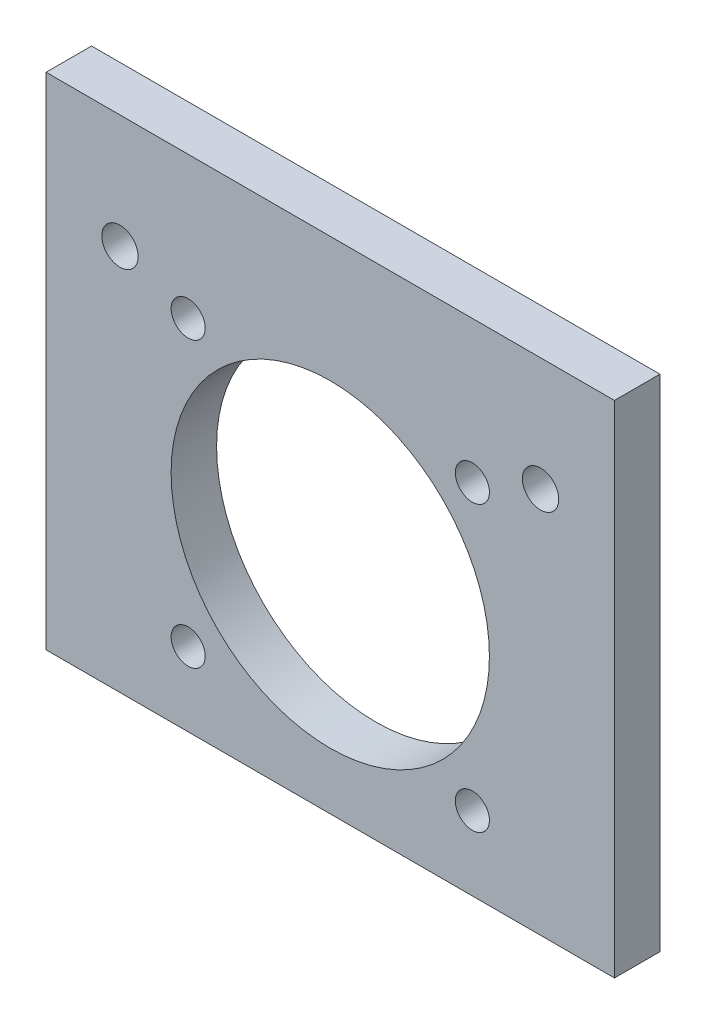
SolidWorks part; units mm, degrees
ref_plane "Płaszczyzna przednia" through (0, 0, 0) normal (0, 0, 1) x (1, 0, 0)
ref_plane "Płaszczyzna górna" through (0, 0, 0) normal (0, 1, 0) x (1, 0, 0)
ref_plane "Płaszczyzna prawa" through (0, 0, 0) normal (1, 0, 0) x (0, 0, -1)
sketch "Sketch1" plane through (0, 0, 0) normal (0, 0, 1) x (1, 0, 0)
  line L1 (0, 0) -> (50, 0)
  line L2 (0, 0) -> (0, 44)
  line L3 (0, 44) -> (50, 44)
  line L4 (50, 0) -> (50, 44)
  dimension "D1" = 50
  dimension "D2" = 44
extrude "Boss-Extrude1" add sketch "Sketch1" along normal blind 4
hole_wizard "Ø3.0mm Dowel Hole1" positions "Sketch2" profile "Sketch3" hole size "Ø3.0" standard "ANSI Metric" end condition through all
sketch "Sketch2" plane through (0, 0, 4) normal (0, 0, 1) x (1, 0, 0)
  line L0 (0, 44) -> (0, 0) construction
  line L1 (50, 44) -> (0, 44) construction
  point P0 (6.5, 34)
  point P2 (43.5, 34)
  dimension "D1" = 37
  dimension "D2" = 6.5
  dimension "D3" = 10
sketch "Sketch3" plane through (6.5, 34, 4) normal (1, 0, 0) x (0, -1, 0)
  line L0 (0, 0) -> (0, 4)
  line L1 (0, 4) -> (1.6, 4)
  line L2 (1.6, 4) -> (1.6, 0)
  line L5 (1.6, 0) -> (0, 0)
  line L11 (0, -6.35) -> (0, 107.95) construction
  dimension "Thru Hole Dia." = 3.2
  dimension "Thru Hole Depth" = 4
sketch "Sketch4" plane through (0, 0, 4) normal (0, 0, 1) x (1, 0, 0)
  line L0 (25, 0) -> (25, 44) construction
  line L1 (0, 0) -> (50, 0) construction
  line L2 (50, 44) -> (0, 44) construction
  circle A0 centre (25, 19) radius 14
  dimension "D1" = 28
  dimension "D2" = 19
extrude "Cut-Extrude1" cut sketch "Sketch4" against normal blind 4
hole_wizard "Ø3.0mm Dowel Hole2" positions "Sketch5" profile "Sketch6" hole size "Ø3.0" standard "ANSI Metric" end condition through all
sketch "Sketch5" plane through (0, 0, 4) normal (0, 0, 1) x (1, 0, 0)
  line L1 (10, 34) -> (40, 34)
  line L2 (10, 34) -> (10, 4)
  line L3 (10, 4) -> (40, 4)
  line L4 (40, 34) -> (40, 4)
  line L5 (10, 34) -> (40, 4) construction
  line L6 (10, 4) -> (40, 34) construction
  line L7 (0, 0) -> (50, 0) construction
  line L8 (0, 44) -> (0, 0) construction
  point P0 (12.5, 31.5)
  point P119 (25, 19)
  point P135 (37.5, 31.5)
  point P136 (37.5, 6.5)
  point P137 (12.5, 6.5)
  dimension "D1" = 30
  dimension "D2" = 4
  dimension "D3" = 10
  dimension "D4" = 2.5
  dimension "D5" = 2.5
  dimension "D6" = 4
sketch "Sketch6" plane through (12.5, 31.5, 4) normal (1, 0, 0) x (0, -1, 0)
  line L0 (0, 0) -> (0, 4)
  line L1 (0, 4) -> (1.5, 4)
  line L2 (1.5, 4) -> (1.5, 0)
  line L5 (1.5, 0) -> (0, 0)
  line L11 (0, -6.35) -> (0, 107.95) construction
  dimension "Thru Hole Dia." = 3
  dimension "Thru Hole Depth" = 4
